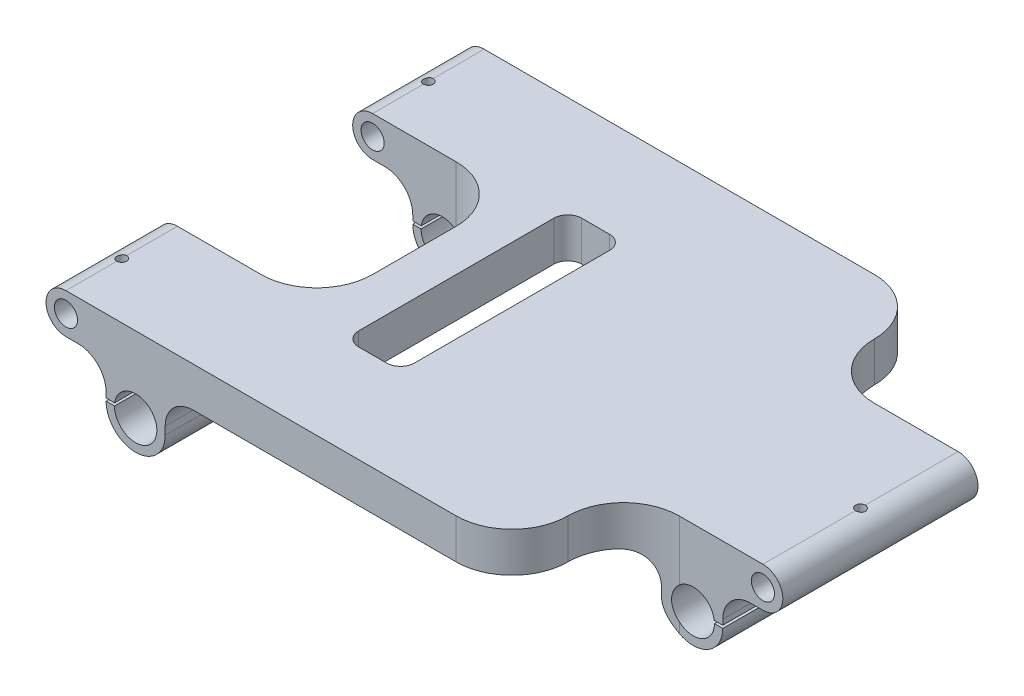
SolidWorks part; units mm, degrees
ref_plane "Front Plane" through (0, 0, 0) normal (0, 0, 1) x (1, 0, 0)
ref_plane "Top Plane" through (0, 0, 0) normal (0, 1, 0) x (1, 0, 0)
ref_plane "Right Plane" through (0, 0, 0) normal (1, 0, 0) x (0, 0, -1)
sketch "Sketch5" plane through (0, 0, 0) normal (0, 0, 1) x (1, 0, 0)
  line L0 (-80, 0) -> (0, 0) construction
  line L1 (0, 0) -> (80, 0) construction
  line L2 (-90.6, 0) -> (-90.6, 12.85)
  line L3 (-90.6, 12.85) -> (-105, 12.85)
  line L5 (0, 0) -> (0, 20) construction
  line L6 (-105, 27.15) -> (105, 27.15)
  line L7 (90.6, 12.85) -> (105, 12.85)
  line L8 (90.6, 0) -> (90.6, 12.85)
  line L9 (-69.4, 0) -> (69.4, 0)
  circle A0 centre (-80, 0) radius 7.6
  circle A1 centre (80, 0) radius 7.6
  circle A2 centre (-105, 20) radius 4.15
  circle A3 centre (105, 20) radius 4.15
  arc A4 (-90.6, 0) -> (-80, -10.6) centre (-80, 0) ccw
  arc A5 (-105, 27.15) -> (-105, 12.85) centre (-105, 20) ccw
  arc A6 (105, 27.15) -> (105, 12.85) centre (105, 20) cw
  arc A7 (90.6, 0) -> (80, -10.6) centre (80, 0) cw
  arc A8 (80, -10.6) -> (69.4, 0) centre (80, 0) cw
  arc A9 (-80, -10.6) -> (-69.4, 0) centre (-80, 0) ccw
  point P11 (0, 27.15)
  point P23 (0, -10.5)
  dimension "D2" = 15.2
  dimension "D3" = 8.3
  dimension "D6" = 8.3
  dimension "D9" = 3
  dimension "D10" = 3
  dimension "D1" = 80
  dimension "D7" = 20
  dimension "D8" = 105
extrude "Boss-Extrude4" add sketch "Sketch5" along normal blind 150
sketch "Sketch7" plane through (0, 27.15, 0) normal (0, 1, 0) x (1, 0, 0)
  line L0 (105, -150) -> (-105, -150) construction
  line L1 (-55, -110) -> (-144.175, -110)
  line L2 (-55, -110) -> (-55, -40)
  line L3 (-55, -40) -> (-144.175, -40)
  line L4 (-144.175, -110) -> (-144.175, -40)
  line L5 (105, 0) -> (-105, 0) construction
  line L6 (-105, -150) -> (-105, 0) construction
  line L8 (105, -150) -> (105, 0) construction
  line L9 (179.0512, -169.1017) -> (55, -169.1017)
  line L10 (179.0512, -169.1017) -> (179.0512, -110)
  line L11 (179.0512, -110) -> (55, -110)
  line L12 (55, -169.1017) -> (55, -110)
  line L13 (147.105, -40) -> (55, -40)
  line L14 (147.105, -40) -> (147.105, 29.543)
  line L15 (147.105, 29.543) -> (55, 29.543)
  line L16 (55, -40) -> (55, 29.543)
  dimension "D1" = 40
  dimension "D2" = 40
  dimension "D3" = 50
  dimension "D4" = 50
extrude "Cut-Extrude3" cut sketch "Sketch7" against normal blind 150
fillet "Fillet2" radius 20 2 edges at (55, 13.575, 0) (55, 13.575, 150)
fillet "Fillet3" radius 20 2 edges at (55, 13.575, 40) (55, 13.575, 110)
fillet "Fillet4" radius 20 2 edges at (-55, 13.575, 40) (-55, 13.575, 110)
sketch "Sketch8" plane through (0, 0, 0) normal (0, -1, 0) x (1, 0, 0)
  line L2 (-45, 150) -> (-69.4, 150)
  line L10 (-69.4, 0) -> (35, 0)
  line L11 (69.4, 39.2) -> (69.4, 110.8)
  line L12 (35, 150) -> (-69.4, 150)
  line L13 (-69.4, 150) -> (-69.4, 109.2)
  line L14 (-55, 90) -> (-55, 60)
  line L15 (-69.4, 40.8) -> (-69.4, 0)
  line L20 (-59.5, 0) -> (35, 0)
  line L21 (69.4, 39.2) -> (69.4, 110.8)
  line L22 (35, 150) -> (-59.5, 150)
  line L23 (-69.4, 150) -> (-69.4, 109.2)
  line L24 (-55, 90) -> (-55, 60)
  line L25 (-69.4, 40.8) -> (-69.4, 0)
  arc A6 (35, 0) -> (55, 20) centre (35, 20) ccw
  arc A7 (69.4, 39.2) -> (55, 20) centre (75, 20) ccw
  arc A8 (55, 130) -> (69.4, 110.8) centre (75, 130) ccw
  arc A9 (55, 130) -> (35, 150) centre (35, 130) ccw
  arc A10 (-55, 90) -> (-69.4, 109.2) centre (-75, 90) ccw
  arc A11 (-69.4, 40.8) -> (-55, 60) centre (-75, 60) ccw
  arc A12 (35, 0) -> (55, 20) centre (35, 20) ccw
  arc A13 (69.4, 39.2) -> (55, 20) centre (75, 20) ccw
  arc A14 (55, 130) -> (69.4, 110.8) centre (75, 130) ccw
  arc A15 (55, 130) -> (35, 150) centre (35, 130) ccw
  arc A16 (-55, 90) -> (-69.4, 109.2) centre (-75, 90) ccw
  arc A17 (-69.4, 40.8) -> (-55, 60) centre (-75, 60) ccw
  dimension "D1" = 0
extrude "Cut-Extrude4" cut sketch "Sketch8" against normal up to surface (12.85 mm away)
ref_plane "Plane3" through (0, 0, 75) normal (0, 0, -1) x (-1, 0, 0)
fillet "Fillet6" radius 10 6 edges at (90.6, 12.85, 75) (69.4, 12.85, 75) (-90.6, 12.85, 20) (-90.6, 12.85, 130) (-69.4, 12.85, 20.4) (-69.4, 12.85, 129.6)
sketch "Sketch12" plane through (0, 27.15, 0) normal (0, 1, 0) x (1, 0, 0)
  line L0 (-105, -40) -> (-105, 0) construction
  line L1 (-105, -150) -> (-105, -110) construction
  line L2 (105, -110) -> (105, -40) construction
  circle A0 centre (-105, -20) radius 1.75
  circle A1 centre (-105, -130) radius 1.75
  circle A2 centre (105, -75) radius 1.75
  dimension "D1" = 3.5
extrude "Cut-Extrude8" cut sketch "Sketch12" against normal blind 208
sketch "Sketch13" plane through (0, 12.85, 0) normal (0, -1, 0) x (-1, 0, 0)
  line L1 (25, -35) -> (35, -35)
  line L2 (20, -40) -> (20, -110)
  line L3 (25, -115) -> (35, -115)
  line L4 (40, -40) -> (40, -110)
  line L5 (55, -90) -> (55, -60) construction
  arc A0 (20, -110) -> (25, -115) centre (25, -110) ccw
  arc A1 (35, -115) -> (40, -110) centre (35, -110) ccw
  arc A2 (35, -35) -> (40, -40) centre (35, -40) cw
  arc A3 (25, -35) -> (20, -40) centre (25, -40) ccw
  point P4 (30, -115)
  point P5 (40, -75)
  point P9 (55, -75)
  point P12 (20, -115)
  point P17 (40, -35)
  point P20 (20, -35)
  dimension "D5" = 5
  dimension "D1" = 20
  dimension "D2" = 65
  dimension "D3" = 80
  dimension "D4" = 0
extrude "Cut-Extrude9" cut sketch "Sketch13" against normal blind 20
sketch "Sketch15" plane through (-90.6, 0, 0) normal (-1, 0, 0) x (0, 0, 1)
  line L0 (150, 0) -> (0, 0)
extrude "Cut-Extrude-Thin1" cut sketch "Sketch15" against normal blind 10 thin thin type one direction wall 1
sketch "Sketch16" plane through (90.6, 0, 0) normal (1, 0, 0) x (0, 0, -1)
  line L0 (-40, 0) -> (-110, 0)
extrude "Cut-Extrude-Thin2" cut sketch "Sketch16" against normal blind 10 thin thin type one direction wall 1
